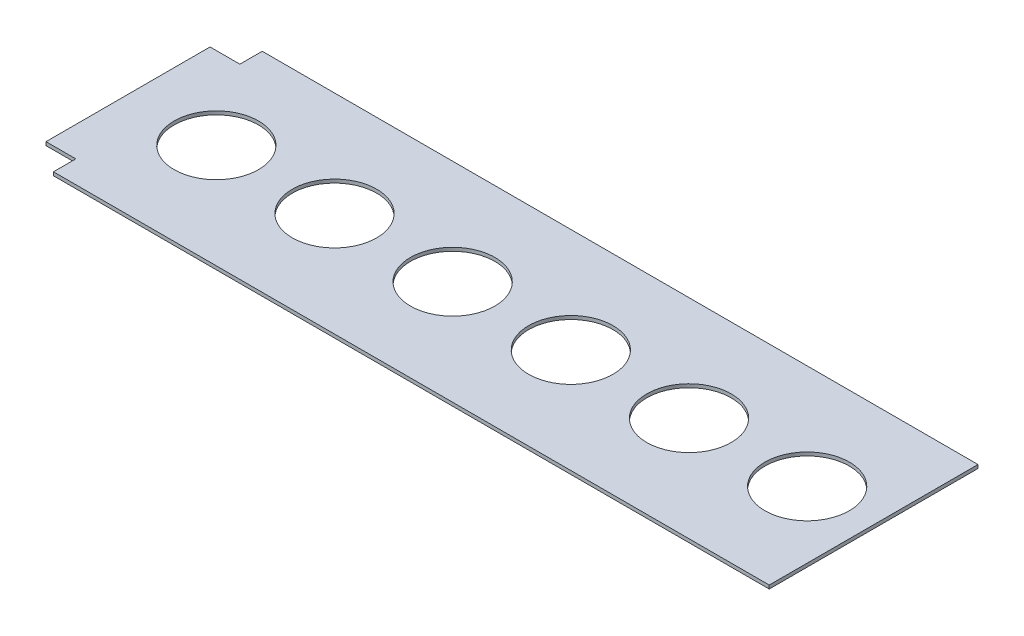
SolidWorks part; units mm, degrees
material "Acrylic (Medium-high impact)"
ref_plane "Front" through (0, 0, 0) normal (0, 0, 1) x (1, 0, 0)
ref_plane "Top" through (0, 0, 0) normal (0, 1, 0) x (1, 0, 0)
ref_plane "Right" through (0, 0, 0) normal (1, 0, 0) x (0, 0, -1)
sketch "Sketch1" plane through (0, 0, 0) normal (0, 1, 0) x (1, 0, 0)
  line L0 (1355.9397, 10.4946) -> (720.9397, 10.4946) construction
  line L5 (1355.9397, 79.0746) -> (1355.9397, -58.0854) construction
  line L6 (720.9397, -58.0854) -> (720.9397, 79.0746) construction
  line L12 (1354.6697, -59.3554) -> (722.2097, -59.3554) construction
  line L13 (746.3397, 99.3946) -> (1355.9397, 99.3946) construction
  line L27 (720.9397, 80.3446) -> (720.9397, -59.3554)
  line L32 (746.3397, -78.4054) -> (1355.9397, -78.4054) construction
  line L44 (1355.9397, 99.3946) -> (1355.9397, -78.4054)
  line L45 (746.3397, 99.3946) -> (1355.9397, -78.4054) construction
  line L50 (746.3397, -78.4054) -> (1355.9397, 99.3946) construction
  line L53 (720.9397, -59.3554) -> (746.3397, -59.3554)
  line L54 (746.3397, -78.4054) -> (746.3397, -59.3554)
  line L58 (720.9397, 80.3446) -> (746.3397, 80.3446)
  line L59 (746.3397, 99.3946) -> (746.3397, 80.3446)
  line L60 (722.2097, 80.3446) -> (1354.6697, 80.3446) construction
  line L61 (1355.9397, -78.4054) -> (746.3397, -78.4054)
  line L62 (1355.9397, 99.3946) -> (746.3397, 99.3946)
  circle A0 centre (1299.3357, 10.4946) radius 35.935
  circle A1 centre (1198.7009, 10.4946) radius 35.935
  circle A2 centre (1098.0661, 10.4946) radius 35.935
  circle A3 centre (997.4313, 10.4946) radius 35.935
  circle A4 centre (896.7965, 10.4946) radius 35.935
  circle A5 centre (796.1617, 10.4946) radius 35.935
  circle A6 centre (1299.3357, 10.4946) radius 33.395 construction
  point P6 (1051.1397, 10.4946)
  dimension "D3" = 2.54
  dimension "D1" = 177.8
  dimension "D2" = 25.4
extrude "Boss-Extrude1" add sketch "Sketch1" along normal blind 2.9718
